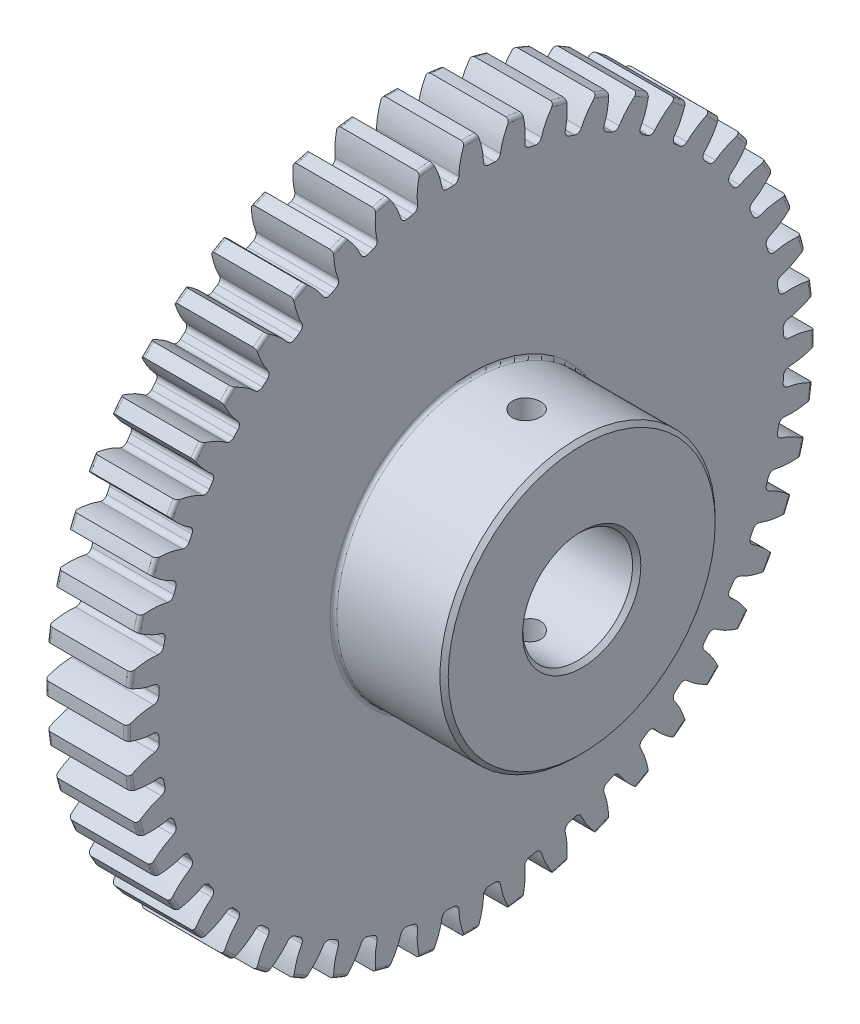
SolidWorks part; units mm, degrees
material "Delrin 2700 NC010, Low Viscosity Acetal Copolymer (SS)"
ref_plane "Front Plane" through (0, 0, 0) normal (0, 0, 1) x (1, 0, 0)
ref_plane "Top Plane" through (0, 0, 0) normal (0, 1, 0) x (1, 0, 0)
ref_plane "Right Plane" through (0, 0, 0) normal (1, 0, 0) x (0, 0, -1)
sketch "Sketch1" plane through (0, 0, 0) normal (0, 0, 1) x (1, 0, 0)
  line L0 (-2.3749, 19.8438) -> (-2.3749, 0)
  line L1 (-2.3749, 0) -> (2.3749, 0)
  line L2 (2.3749, 0) -> (2.3749, 19.8438)
  line L3 (2.3749, 19.8438) -> (-2.3749, 19.8438)
  line L4 (-2.3749, 0) -> (2.3749, 0) construction
revolve "Revolve1" add sketch "Sketch1" angle 360 about L4 reverse direction yes
sketch "Sketch2" plane through (-2.3749, 0, 0) normal (-1, 0, 0) x (0, 0, 1)
  arc A0 (0.7316, 18.0319) -> (1.6283, 17.9731) centre (0, 0) cw
  arc A1 (2.2123, 19.72) -> (0.3806, 19.8401) centre (0, 0) ccw
  spline S0 degree 3 poles (0.3806, 19.8401) (0.4054, 19.7738) (0.4294, 19.7071) (0.4523, 19.6401) (0.5249, 19.4282) (0.5865, 19.212) (0.6329, 18.9928) (0.6803, 18.7688) (0.6967, 18.5388) (0.7099, 18.3101) (0.7153, 18.2172) (0.7242, 18.1246) (0.7316, 18.0319) knots -0.000212 -0.000212 -0.000212 -0.000212 0 0 0 0.000672 0.000672 0.000672 0.001361 0.001361 0.001361 0.00164 0.00164 0.00164 0.00164
  spline S1 degree 3 poles (1.6283, 17.9731) (1.6477, 18.0641) (1.6686, 18.1548) (1.6861, 18.2461) (1.7281, 18.4663) (1.7727, 18.6874) (1.8467, 18.8989) (1.9223, 19.115) (2.0133, 19.326) (2.1151, 19.5311) (2.1466, 19.5946) (2.179, 19.6575) (2.2123, 19.72) knots -0.000279 -0.000279 -0.000279 -0.000279 0 0 0 0.000672 0.000672 0.000672 0.001357 0.001357 0.001357 0.001569 0.001569 0.001569 0.001569
extrude "Cut-Extrude1" cut sketch "Sketch2" against normal through all
sketch "Sketch3" plane through (-2.3749, 0, 0) normal (-1, 0, 0) x (0, 0, 1)
  arc A0 (3.079, 17.7821) -> (3.9603, 17.6068) centre (0, 0) cw
  arc A1 (4.7674, 19.2626) -> (2.967, 19.6207) centre (0, 0) ccw
  spline S0 degree 3 poles (2.967, 19.6207) (2.983, 19.5517) (2.998, 19.4825) (3.012, 19.413) (3.0562, 19.1935) (3.0891, 18.9711) (3.1065, 18.7477) (3.1243, 18.5194) (3.1106, 18.2892) (3.0938, 18.0608) (3.087, 17.968) (3.0838, 17.875) (3.079, 17.7821) knots -0.000212 -0.000212 -0.000212 -0.000212 0 0 0 0.000672 0.000672 0.000672 0.001361 0.001361 0.001361 0.00164 0.00164 0.00164 0.00164
  spline S1 degree 3 poles (3.9603, 17.6068) (3.9914, 17.6945) (4.024, 17.7816) (4.0533, 17.87) (4.1236, 18.0827) (4.1967, 18.2962) (4.2977, 18.4962) (4.4008, 18.7006) (4.5187, 18.8979) (4.6463, 19.088) (4.6858, 19.1467) (4.7262, 19.2049) (4.7674, 19.2626) knots -0.000279 -0.000279 -0.000279 -0.000279 0 0 0 0.000672 0.000672 0.000672 0.001357 0.001357 0.001357 0.001569 0.001569 0.001569 0.001569
extrude "Cut-Extrude2" cut sketch "Sketch3" against normal through all
sketch "Sketch4" plane through (-2.3749, 0, 0) normal (-1, 0, 0) x (0, 0, 1)
  arc A0 (5.3737, 17.2281) -> (6.2246, 16.9392) centre (0, 0) cw
  arc A1 (7.2408, 18.4755) -> (5.5026, 19.0656) centre (0, 0) ccw
  spline S0 degree 3 poles (5.5026, 19.0656) (5.5094, 18.9951) (5.5153, 18.9245) (5.5201, 18.8538) (5.5354, 18.6303) (5.5389, 18.4055) (5.527, 18.1819) (5.5148, 17.9532) (5.4712, 17.7267) (5.4248, 17.5025) (5.4059, 17.4114) (5.3906, 17.3196) (5.3737, 17.2281) knots -0.000212 -0.000212 -0.000212 -0.000212 0 0 0 0.000672 0.000672 0.000672 0.001361 0.001361 0.001361 0.00164 0.00164 0.00164 0.00164
  spline S1 degree 3 poles (6.2246, 16.9392) (6.2669, 17.0221) (6.3106, 17.1043) (6.3511, 17.188) (6.4486, 17.3898) (6.5489, 17.5918) (6.6752, 17.777) (6.8041, 17.9662) (6.9467, 18.1464) (7.0981, 18.3182) (7.1449, 18.3713) (7.1925, 18.4237) (7.2408, 18.4755) knots -0.000279 -0.000279 -0.000279 -0.000279 0 0 0 0.000672 0.000672 0.000672 0.001357 0.001357 0.001357 0.001569 0.001569 0.001569 0.001569
extrude "Cut-Extrude3" cut sketch "Sketch4" against normal through all
sketch "Sketch5" plane through (-2.3749, 0, 0) normal (-1, 0, 0) x (0, 0, 1)
  arc A0 (7.5764, 16.3793) -> (8.3824, 15.9819) centre (0, 0) cw
  arc A1 (9.5904, 17.3723) -> (7.9441, 18.1842) centre (0, 0) ccw
  spline S0 degree 3 poles (7.9441, 18.1842) (7.9417, 18.1134) (7.9383, 18.0427) (7.9338, 17.972) (7.9197, 17.7484) (7.894, 17.5251) (7.8529, 17.3049) (7.811, 17.0798) (7.7382, 16.8609) (7.6629, 16.6447) (7.6323, 16.5568) (7.6051, 16.4678) (7.5764, 16.3793) knots -0.000212 -0.000212 -0.000212 -0.000212 0 0 0 0.000672 0.000672 0.000672 0.001361 0.001361 0.001361 0.00164 0.00164 0.00164 0.00164
  spline S1 degree 3 poles (8.3824, 15.9819) (8.4351, 16.0585) (8.4892, 16.1342) (8.5402, 16.212) (8.6633, 16.3993) (8.7891, 16.5865) (8.9384, 16.7536) (9.091, 16.9244) (9.2558, 17.0845) (9.4283, 17.235) (9.4817, 17.2816) (9.5358, 17.3273) (9.5904, 17.3723) knots -0.000279 -0.000279 -0.000279 -0.000279 0 0 0 0.000672 0.000672 0.000672 0.001357 0.001357 0.001357 0.001569 0.001569 0.001569 0.001569
extrude "Cut-Extrude4" cut sketch "Sketch5" against normal through all
sketch "Sketch6" plane through (-2.3749, 0, 0) normal (-1, 0, 0) x (0, 0, 1)
  arc A0 (9.6495, 15.2503) -> (10.3967, 14.751) centre (0, 0) cw
  arc A1 (11.7759, 15.9719) -> (10.2497, 16.9917) centre (0, 0) ccw
  spline S0 degree 3 poles (10.2497, 16.9917) (10.238, 16.9219) (10.2254, 16.8522) (10.2118, 16.7827) (10.1686, 16.5629) (10.1139, 16.3448) (10.0445, 16.1318) (9.9735, 15.9141) (9.8728, 15.7067) (9.7699, 15.5021) (9.7281, 15.4189) (9.6895, 15.3342) (9.6495, 15.2503) knots -0.000212 -0.000212 -0.000212 -0.000212 0 0 0 0.000672 0.000672 0.000672 0.001361 0.001361 0.001361 0.00164 0.00164 0.00164 0.00164
  spline S1 degree 3 poles (10.3967, 14.751) (10.459, 14.8201) (10.5225, 14.8882) (10.5833, 14.9586) (10.7297, 15.1282) (10.8789, 15.2974) (11.0487, 15.4436) (11.2223, 15.593) (11.4066, 15.7302) (11.5973, 15.8569) (11.6563, 15.8961) (11.7159, 15.9344) (11.7759, 15.9719) knots -0.000279 -0.000279 -0.000279 -0.000279 0 0 0 0.000672 0.000672 0.000672 0.001357 0.001357 0.001357 0.001569 0.001569 0.001569 0.001569
extrude "Cut-Extrude5" cut sketch "Sketch6" against normal through all
sketch "Sketch7" plane through (-2.3749, 0, 0) normal (-1, 0, 0) x (0, 0, 1)
  arc A0 (11.5575, 13.8603) -> (12.2331, 13.2678) centre (0, 0) cw
  arc A1 (13.7599, 14.2982) -> (12.3798, 15.5085) centre (0, 0) ccw
  spline S0 degree 3 poles (12.3798, 15.5085) (12.3592, 15.4408) (12.3376, 15.3733) (12.315, 15.3062) (12.2435, 15.0939) (12.1608, 14.8848) (12.0642, 14.6828) (11.9654, 14.4761) (11.8384, 14.2836) (11.7097, 14.0942) (11.6574, 14.0173) (11.6081, 13.9383) (11.5575, 13.8603) knots -0.000212 -0.000212 -0.000212 -0.000212 0 0 0 0.000672 0.000672 0.000672 0.001361 0.001361 0.001361 0.00164 0.00164 0.00164 0.00164
  spline S1 degree 3 poles (12.2331, 13.2678) (12.3039, 13.3282) (12.3757, 13.3873) (12.4452, 13.4492) (12.6125, 13.5983) (12.7825, 13.7466) (12.97, 13.8693) (13.1615, 13.9948) (13.3622, 14.1067) (13.5678, 14.2075) (13.6314, 14.2387) (13.6955, 14.2689) (13.7599, 14.2982) knots -0.000279 -0.000279 -0.000279 -0.000279 0 0 0 0.000672 0.000672 0.000672 0.001357 0.001357 0.001357 0.001569 0.001569 0.001569 0.001569
extrude "Cut-Extrude6" cut sketch "Sketch7" against normal through all
sketch "Sketch8" plane through (-2.3749, 0, 0) normal (-1, 0, 0) x (0, 0, 1)
  arc A0 (13.2678, 12.2331) -> (13.8603, 11.5575) centre (0, 0) cw
  arc A1 (15.5085, 12.3798) -> (14.2982, 13.7599) centre (0, 0) ccw
  spline S0 degree 3 poles (14.2982, 13.7599) (14.2689, 13.6955) (14.2387, 13.6314) (14.2075, 13.5678) (14.1089, 13.3667) (13.9996, 13.1702) (13.8775, 12.9824) (13.7526, 12.7905) (13.6016, 12.6162) (13.4492, 12.4452) (13.3873, 12.3757) (13.3282, 12.3039) (13.2678, 12.2331) knots -0.000212 -0.000212 -0.000212 -0.000212 0 0 0 0.000672 0.000672 0.000672 0.001361 0.001361 0.001361 0.00164 0.00164 0.00164 0.00164
  spline S1 degree 3 poles (13.8603, 11.5575) (13.9383, 11.6081) (14.0173, 11.6574) (14.0942, 11.7097) (14.2796, 11.8357) (14.4675, 11.9605) (14.6694, 12.0578) (14.8756, 12.1571) (15.0892, 12.2419) (15.3062, 12.315) (15.3733, 12.3376) (15.4408, 12.3592) (15.5085, 12.3798) knots -0.000279 -0.000279 -0.000279 -0.000279 0 0 0 0.000672 0.000672 0.000672 0.001357 0.001357 0.001357 0.001569 0.001569 0.001569 0.001569
extrude "Cut-Extrude7" cut sketch "Sketch8" against normal through all
sketch "Sketch9" plane through (-2.3749, 0, 0) normal (-1, 0, 0) x (0, 0, 1)
  arc A0 (14.751, 10.3967) -> (15.2503, 9.6495) centre (0, 0) cw
  arc A1 (16.9917, 10.2497) -> (15.9719, 11.7759) centre (0, 0) ccw
  spline S0 degree 3 poles (15.9719, 11.7759) (15.9344, 11.7159) (15.8961, 11.6563) (15.8569, 11.5973) (15.7329, 11.4107) (15.5989, 11.2302) (15.4533, 11.06) (15.3044, 10.886) (15.1319, 10.7329) (14.9586, 10.5833) (14.8882, 10.5225) (14.8201, 10.459) (14.751, 10.3967) knots -0.000212 -0.000212 -0.000212 -0.000212 0 0 0 0.000672 0.000672 0.000672 0.001361 0.001361 0.001361 0.00164 0.00164 0.00164 0.00164
  spline S1 degree 3 poles (15.2503, 9.6495) (15.3342, 9.6895) (15.4189, 9.7281) (15.5021, 9.7699) (15.7023, 9.8706) (15.9049, 9.9698) (16.1177, 10.0399) (16.3352, 10.1114) (16.558, 10.1677) (16.7827, 10.2118) (16.8522, 10.2254) (16.9219, 10.238) (16.9917, 10.2497) knots -0.000279 -0.000279 -0.000279 -0.000279 0 0 0 0.000672 0.000672 0.000672 0.001357 0.001357 0.001357 0.001569 0.001569 0.001569 0.001569
extrude "Cut-Extrude8" cut sketch "Sketch9" against normal through all
sketch "Sketch10" plane through (-2.3749, 0, 0) normal (-1, 0, 0) x (0, 0, 1)
  arc A0 (15.9819, 8.3824) -> (16.3793, 7.5764) centre (0, 0) cw
  arc A1 (18.1842, 7.9441) -> (17.3723, 9.5904) centre (0, 0) ccw
  spline S0 degree 3 poles (17.3723, 9.5904) (17.3273, 9.5358) (17.2816, 9.4817) (17.235, 9.4283) (17.0877, 9.2596) (16.9313, 9.0981) (16.7647, 8.9483) (16.5944, 8.7953) (16.4034, 8.666) (16.212, 8.5402) (16.1342, 8.4892) (16.0585, 8.4351) (15.9819, 8.3824) knots -0.000212 -0.000212 -0.000212 -0.000212 0 0 0 0.000672 0.000672 0.000672 0.001361 0.001361 0.001361 0.00164 0.00164 0.00164 0.00164
  spline S1 degree 3 poles (16.3793, 7.5764) (16.4678, 7.6051) (16.5568, 7.6323) (16.6447, 7.6629) (16.8563, 7.7366) (17.0701, 7.8085) (17.2903, 7.8502) (17.5152, 7.8928) (17.7435, 7.9194) (17.972, 7.9338) (18.0427, 7.9383) (18.1134, 7.9417) (18.1842, 7.9441) knots -0.000279 -0.000279 -0.000279 -0.000279 0 0 0 0.000672 0.000672 0.000672 0.001357 0.001357 0.001357 0.001569 0.001569 0.001569 0.001569
extrude "Cut-Extrude9" cut sketch "Sketch10" against normal through all
sketch "Sketch11" plane through (-2.3749, 0, 0) normal (-1, 0, 0) x (0, 0, 1)
  arc A0 (16.9392, 6.2246) -> (17.2281, 5.3737) centre (0, 0) cw
  arc A1 (19.0656, 5.5026) -> (18.4755, 7.2408) centre (0, 0) ccw
  spline S0 degree 3 poles (18.4755, 7.2408) (18.4237, 7.1925) (18.3713, 7.1449) (18.3182, 7.0981) (18.1501, 6.9499) (17.974, 6.8102) (17.7893, 6.6835) (17.6004, 6.554) (17.3942, 6.4508) (17.188, 6.3511) (17.1043, 6.3106) (17.0221, 6.2669) (16.9392, 6.2246) knots -0.000212 -0.000212 -0.000212 -0.000212 0 0 0 0.000672 0.000672 0.000672 0.001361 0.001361 0.001361 0.00164 0.00164 0.00164 0.00164
  spline S1 degree 3 poles (17.2281, 5.3737) (17.3196, 5.3906) (17.4114, 5.4059) (17.5025, 5.4248) (17.7219, 5.4702) (17.9433, 5.5136) (18.167, 5.5262) (18.3956, 5.539) (18.6254, 5.5357) (18.8538, 5.5201) (18.9245, 5.5153) (18.9951, 5.5094) (19.0656, 5.5026) knots -0.000279 -0.000279 -0.000279 -0.000279 0 0 0 0.000672 0.000672 0.000672 0.001357 0.001357 0.001357 0.001569 0.001569 0.001569 0.001569
extrude "Cut-Extrude10" cut sketch "Sketch11" against normal through all
sketch "Sketch12" plane through (-2.3749, 0, 0) normal (-1, 0, 0) x (0, 0, 1)
  arc A0 (17.6068, 3.9603) -> (17.7821, 3.079) centre (0, 0) cw
  arc A1 (19.6207, 2.967) -> (19.2626, 4.7674) centre (0, 0) ccw
  spline S0 degree 3 poles (19.2626, 4.7674) (19.2049, 4.7262) (19.1467, 4.6858) (19.088, 4.6463) (18.902, 4.5214) (18.7091, 4.4059) (18.5095, 4.3044) (18.3053, 4.2006) (18.0874, 4.1252) (17.87, 4.0533) (17.7816, 4.024) (17.6945, 3.9914) (17.6068, 3.9603) knots -0.000212 -0.000212 -0.000212 -0.000212 0 0 0 0.000672 0.000672 0.000672 0.001361 0.001361 0.001361 0.00164 0.00164 0.00164 0.00164
  spline S1 degree 3 poles (17.7821, 3.079) (17.875, 3.0838) (17.968, 3.087) (18.0608, 3.0938) (18.2843, 3.1102) (18.5095, 3.1244) (18.7329, 3.1076) (18.9612, 3.0906) (19.1886, 3.0572) (19.413, 3.012) (19.4825, 2.998) (19.5517, 2.983) (19.6207, 2.967) knots -0.000279 -0.000279 -0.000279 -0.000279 0 0 0 0.000672 0.000672 0.000672 0.001357 0.001357 0.001357 0.001569 0.001569 0.001569 0.001569
extrude "Cut-Extrude11" cut sketch "Sketch12" against normal through all
sketch "Sketch13" plane through (-2.3749, 0, 0) normal (-1, 0, 0) x (0, 0, 1)
  arc A0 (17.9731, 1.6283) -> (18.0319, 0.7316) centre (0, 0) cw
  arc A1 (19.8401, 0.3806) -> (19.72, 2.2123) centre (0, 0) ccw
  spline S0 degree 3 poles (19.72, 2.2123) (19.6575, 2.179) (19.5946, 2.1466) (19.5311, 2.1151) (19.3305, 2.0155) (19.1242, 1.9262) (18.9129, 1.8516) (18.697, 1.7754) (18.4711, 1.729) (18.2461, 1.6861) (18.1548, 1.6686) (18.0641, 1.6477) (17.9731, 1.6283) knots -0.000212 -0.000212 -0.000212 -0.000212 0 0 0 0.000672 0.000672 0.000672 0.001361 0.001361 0.001361 0.00164 0.00164 0.00164 0.00164
  spline S1 degree 3 poles (18.0319, 0.7316) (18.1246, 0.7243) (18.2172, 0.7153) (18.3101, 0.7099) (18.5338, 0.697) (18.7589, 0.6817) (18.9783, 0.6359) (19.2024, 0.5892) (19.4235, 0.5265) (19.6401, 0.4523) (19.7071, 0.4294) (19.7738, 0.4054) (19.8401, 0.3806) knots -0.000279 -0.000279 -0.000279 -0.000279 0 0 0 0.000672 0.000672 0.000672 0.001357 0.001357 0.001357 0.001569 0.001569 0.001569 0.001569
extrude "Cut-Extrude12" cut sketch "Sketch13" against normal through all
sketch "Sketch14" plane through (-2.3749, 0, 0) normal (-1, 0, 0) x (0, 0, 1)
  arc A0 (18.0319, -0.7316) -> (17.9731, -1.6283) centre (0, 0) cw
  arc A1 (19.72, -2.2123) -> (19.8401, -0.3806) centre (0, 0) ccw
  spline S0 degree 3 poles (19.8401, -0.3806) (19.7738, -0.4054) (19.7071, -0.4294) (19.6401, -0.4523) (19.4282, -0.5249) (19.212, -0.5865) (18.9928, -0.6329) (18.7688, -0.6803) (18.5388, -0.6967) (18.3101, -0.7099) (18.2172, -0.7153) (18.1246, -0.7242) (18.0319, -0.7316) knots -0.000212 -0.000212 -0.000212 -0.000212 0 0 0 0.000672 0.000672 0.000672 0.001361 0.001361 0.001361 0.00164 0.00164 0.00164 0.00164
  spline S1 degree 3 poles (17.9731, -1.6283) (18.0641, -1.6477) (18.1548, -1.6686) (18.2461, -1.6861) (18.4663, -1.7281) (18.6874, -1.7727) (18.8989, -1.8467) (19.115, -1.9223) (19.326, -2.0133) (19.5311, -2.1151) (19.5946, -2.1466) (19.6575, -2.179) (19.72, -2.2123) knots -0.000279 -0.000279 -0.000279 -0.000279 0 0 0 0.000672 0.000672 0.000672 0.001357 0.001357 0.001357 0.001569 0.001569 0.001569 0.001569
extrude "Cut-Extrude13" cut sketch "Sketch14" against normal through all
sketch "Sketch15" plane through (-2.3749, 0, 0) normal (-1, 0, 0) x (0, 0, 1)
  arc A0 (17.7821, -3.079) -> (17.6068, -3.9603) centre (0, 0) cw
  arc A1 (19.2626, -4.7674) -> (19.6207, -2.967) centre (0, 0) ccw
  spline S0 degree 3 poles (19.6207, -2.967) (19.5517, -2.983) (19.4825, -2.998) (19.413, -3.012) (19.1935, -3.0562) (18.9711, -3.0891) (18.7477, -3.1065) (18.5194, -3.1243) (18.2892, -3.1106) (18.0608, -3.0938) (17.968, -3.087) (17.875, -3.0838) (17.7821, -3.079) knots -0.000212 -0.000212 -0.000212 -0.000212 0 0 0 0.000672 0.000672 0.000672 0.001361 0.001361 0.001361 0.00164 0.00164 0.00164 0.00164
  spline S1 degree 3 poles (17.6068, -3.9603) (17.6945, -3.9914) (17.7816, -4.024) (17.87, -4.0533) (18.0827, -4.1236) (18.2962, -4.1967) (18.4962, -4.2977) (18.7006, -4.4008) (18.8979, -4.5187) (19.088, -4.6463) (19.1467, -4.6858) (19.2049, -4.7262) (19.2626, -4.7674) knots -0.000279 -0.000279 -0.000279 -0.000279 0 0 0 0.000672 0.000672 0.000672 0.001357 0.001357 0.001357 0.001569 0.001569 0.001569 0.001569
extrude "Cut-Extrude14" cut sketch "Sketch15" against normal through all
sketch "Sketch16" plane through (-2.3749, 0, 0) normal (-1, 0, 0) x (0, 0, 1)
  arc A0 (17.2281, -5.3737) -> (16.9392, -6.2246) centre (0, 0) cw
  arc A1 (18.4755, -7.2408) -> (19.0656, -5.5026) centre (0, 0) ccw
  spline S0 degree 3 poles (19.0656, -5.5026) (18.9951, -5.5094) (18.9245, -5.5153) (18.8538, -5.5201) (18.6303, -5.5354) (18.4055, -5.5389) (18.1819, -5.527) (17.9532, -5.5148) (17.7267, -5.4712) (17.5025, -5.4248) (17.4114, -5.4059) (17.3196, -5.3906) (17.2281, -5.3737) knots -0.000212 -0.000212 -0.000212 -0.000212 0 0 0 0.000672 0.000672 0.000672 0.001361 0.001361 0.001361 0.00164 0.00164 0.00164 0.00164
  spline S1 degree 3 poles (16.9392, -6.2246) (17.0221, -6.2669) (17.1043, -6.3106) (17.188, -6.3511) (17.3898, -6.4486) (17.5918, -6.5489) (17.777, -6.6752) (17.9662, -6.8041) (18.1464, -6.9467) (18.3182, -7.0981) (18.3713, -7.1449) (18.4237, -7.1925) (18.4755, -7.2408) knots -0.000279 -0.000279 -0.000279 -0.000279 0 0 0 0.000672 0.000672 0.000672 0.001357 0.001357 0.001357 0.001569 0.001569 0.001569 0.001569
extrude "Cut-Extrude15" cut sketch "Sketch16" against normal through all
sketch "Sketch17" plane through (-2.3749, 0, 0) normal (-1, 0, 0) x (0, 0, 1)
  arc A0 (16.3793, -7.5764) -> (15.9819, -8.3824) centre (0, 0) cw
  arc A1 (17.3723, -9.5904) -> (18.1842, -7.9441) centre (0, 0) ccw
  spline S0 degree 3 poles (18.1842, -7.9441) (18.1134, -7.9417) (18.0427, -7.9383) (17.972, -7.9338) (17.7484, -7.9197) (17.5251, -7.894) (17.3049, -7.8529) (17.0798, -7.811) (16.8609, -7.7382) (16.6447, -7.6629) (16.5568, -7.6323) (16.4678, -7.6051) (16.3793, -7.5764) knots -0.000212 -0.000212 -0.000212 -0.000212 0 0 0 0.000672 0.000672 0.000672 0.001361 0.001361 0.001361 0.00164 0.00164 0.00164 0.00164
  spline S1 degree 3 poles (15.9819, -8.3824) (16.0585, -8.4351) (16.1342, -8.4892) (16.212, -8.5402) (16.3993, -8.6633) (16.5865, -8.7891) (16.7536, -8.9384) (16.9244, -9.091) (17.0845, -9.2558) (17.235, -9.4283) (17.2816, -9.4817) (17.3273, -9.5358) (17.3723, -9.5904) knots -0.000279 -0.000279 -0.000279 -0.000279 0 0 0 0.000672 0.000672 0.000672 0.001357 0.001357 0.001357 0.001569 0.001569 0.001569 0.001569
extrude "Cut-Extrude16" cut sketch "Sketch17" against normal through all
sketch "Sketch18" plane through (-2.3749, 0, 0) normal (-1, 0, 0) x (0, 0, 1)
  arc A0 (15.2503, -9.6495) -> (14.751, -10.3967) centre (0, 0) cw
  arc A1 (15.9719, -11.7759) -> (16.9917, -10.2497) centre (0, 0) ccw
  spline S0 degree 3 poles (16.9917, -10.2497) (16.9219, -10.238) (16.8522, -10.2254) (16.7827, -10.2118) (16.5629, -10.1686) (16.3448, -10.1139) (16.1318, -10.0445) (15.9141, -9.9735) (15.7067, -9.8728) (15.5021, -9.7699) (15.4189, -9.7281) (15.3342, -9.6895) (15.2503, -9.6495) knots -0.000212 -0.000212 -0.000212 -0.000212 0 0 0 0.000672 0.000672 0.000672 0.001361 0.001361 0.001361 0.00164 0.00164 0.00164 0.00164
  spline S1 degree 3 poles (14.751, -10.3967) (14.8201, -10.459) (14.8882, -10.5225) (14.9586, -10.5833) (15.1282, -10.7297) (15.2974, -10.8789) (15.4436, -11.0487) (15.593, -11.2223) (15.7302, -11.4066) (15.8569, -11.5973) (15.8961, -11.6563) (15.9344, -11.7159) (15.9719, -11.7759) knots -0.000279 -0.000279 -0.000279 -0.000279 0 0 0 0.000672 0.000672 0.000672 0.001357 0.001357 0.001357 0.001569 0.001569 0.001569 0.001569
extrude "Cut-Extrude17" cut sketch "Sketch18" against normal through all
sketch "Sketch19" plane through (-2.3749, 0, 0) normal (-1, 0, 0) x (0, 0, 1)
  arc A0 (13.8603, -11.5575) -> (13.2678, -12.2331) centre (0, 0) cw
  arc A1 (14.2982, -13.7599) -> (15.5085, -12.3798) centre (0, 0) ccw
  spline S0 degree 3 poles (15.5085, -12.3798) (15.4408, -12.3592) (15.3733, -12.3376) (15.3062, -12.315) (15.0939, -12.2435) (14.8848, -12.1608) (14.6828, -12.0642) (14.4761, -11.9654) (14.2836, -11.8384) (14.0942, -11.7097) (14.0173, -11.6574) (13.9383, -11.6081) (13.8603, -11.5575) knots -0.000212 -0.000212 -0.000212 -0.000212 0 0 0 0.000672 0.000672 0.000672 0.001361 0.001361 0.001361 0.00164 0.00164 0.00164 0.00164
  spline S1 degree 3 poles (13.2678, -12.2331) (13.3282, -12.3039) (13.3873, -12.3757) (13.4492, -12.4452) (13.5983, -12.6125) (13.7466, -12.7825) (13.8693, -12.97) (13.9948, -13.1615) (14.1067, -13.3622) (14.2075, -13.5678) (14.2387, -13.6314) (14.2689, -13.6955) (14.2982, -13.7599) knots -0.000279 -0.000279 -0.000279 -0.000279 0 0 0 0.000672 0.000672 0.000672 0.001357 0.001357 0.001357 0.001569 0.001569 0.001569 0.001569
extrude "Cut-Extrude18" cut sketch "Sketch19" against normal through all
sketch "Sketch20" plane through (-2.3749, 0, 0) normal (-1, 0, 0) x (0, 0, 1)
  arc A0 (12.2331, -13.2678) -> (11.5575, -13.8603) centre (0, 0) cw
  arc A1 (12.3798, -15.5085) -> (13.7599, -14.2982) centre (0, 0) ccw
  spline S0 degree 3 poles (13.7599, -14.2982) (13.6955, -14.2689) (13.6314, -14.2387) (13.5678, -14.2075) (13.3667, -14.1089) (13.1702, -13.9996) (12.9824, -13.8775) (12.7905, -13.7526) (12.6162, -13.6016) (12.4452, -13.4492) (12.3757, -13.3873) (12.3039, -13.3282) (12.2331, -13.2678) knots -0.000212 -0.000212 -0.000212 -0.000212 0 0 0 0.000672 0.000672 0.000672 0.001361 0.001361 0.001361 0.00164 0.00164 0.00164 0.00164
  spline S1 degree 3 poles (11.5575, -13.8603) (11.6081, -13.9383) (11.6574, -14.0173) (11.7097, -14.0942) (11.8357, -14.2796) (11.9605, -14.4675) (12.0578, -14.6694) (12.1571, -14.8756) (12.2419, -15.0892) (12.315, -15.3062) (12.3376, -15.3733) (12.3592, -15.4408) (12.3798, -15.5085) knots -0.000279 -0.000279 -0.000279 -0.000279 0 0 0 0.000672 0.000672 0.000672 0.001357 0.001357 0.001357 0.001569 0.001569 0.001569 0.001569
extrude "Cut-Extrude19" cut sketch "Sketch20" against normal through all
sketch "Sketch21" plane through (-2.3749, 0, 0) normal (-1, 0, 0) x (0, 0, 1)
  arc A0 (10.3967, -14.751) -> (9.6495, -15.2503) centre (0, 0) cw
  arc A1 (10.2497, -16.9917) -> (11.7759, -15.9719) centre (0, 0) ccw
  spline S0 degree 3 poles (11.7759, -15.9719) (11.7159, -15.9344) (11.6563, -15.8961) (11.5973, -15.8569) (11.4107, -15.7329) (11.2302, -15.5989) (11.06, -15.4533) (10.886, -15.3044) (10.7329, -15.1319) (10.5833, -14.9586) (10.5225, -14.8882) (10.459, -14.8201) (10.3967, -14.751) knots -0.000212 -0.000212 -0.000212 -0.000212 0 0 0 0.000672 0.000672 0.000672 0.001361 0.001361 0.001361 0.00164 0.00164 0.00164 0.00164
  spline S1 degree 3 poles (9.6495, -15.2503) (9.6895, -15.3342) (9.7281, -15.4189) (9.7699, -15.5021) (9.8706, -15.7023) (9.9698, -15.9049) (10.0399, -16.1177) (10.1114, -16.3352) (10.1677, -16.558) (10.2118, -16.7827) (10.2254, -16.8522) (10.238, -16.9219) (10.2497, -16.9917) knots -0.000279 -0.000279 -0.000279 -0.000279 0 0 0 0.000672 0.000672 0.000672 0.001357 0.001357 0.001357 0.001569 0.001569 0.001569 0.001569
extrude "Cut-Extrude20" cut sketch "Sketch21" against normal through all
sketch "Sketch22" plane through (-2.3749, 0, 0) normal (-1, 0, 0) x (0, 0, 1)
  arc A0 (8.3824, -15.9819) -> (7.5764, -16.3793) centre (0, 0) cw
  arc A1 (7.9441, -18.1842) -> (9.5904, -17.3723) centre (0, 0) ccw
  spline S0 degree 3 poles (9.5904, -17.3723) (9.5358, -17.3273) (9.4817, -17.2816) (9.4283, -17.235) (9.2596, -17.0877) (9.0981, -16.9313) (8.9483, -16.7647) (8.7953, -16.5944) (8.666, -16.4034) (8.5402, -16.212) (8.4892, -16.1342) (8.4351, -16.0585) (8.3824, -15.9819) knots -0.000212 -0.000212 -0.000212 -0.000212 0 0 0 0.000672 0.000672 0.000672 0.001361 0.001361 0.001361 0.00164 0.00164 0.00164 0.00164
  spline S1 degree 3 poles (7.5764, -16.3793) (7.6051, -16.4678) (7.6323, -16.5568) (7.6629, -16.6447) (7.7366, -16.8563) (7.8085, -17.0701) (7.8502, -17.2903) (7.8928, -17.5152) (7.9194, -17.7435) (7.9338, -17.972) (7.9383, -18.0427) (7.9417, -18.1134) (7.9441, -18.1842) knots -0.000279 -0.000279 -0.000279 -0.000279 0 0 0 0.000672 0.000672 0.000672 0.001357 0.001357 0.001357 0.001569 0.001569 0.001569 0.001569
extrude "Cut-Extrude21" cut sketch "Sketch22" against normal through all
sketch "Sketch23" plane through (-2.3749, 0, 0) normal (-1, 0, 0) x (0, 0, 1)
  arc A0 (6.2246, -16.9392) -> (5.3737, -17.2281) centre (0, 0) cw
  arc A1 (5.5026, -19.0656) -> (7.2408, -18.4755) centre (0, 0) ccw
  spline S0 degree 3 poles (7.2408, -18.4755) (7.1925, -18.4237) (7.1449, -18.3713) (7.0981, -18.3182) (6.9499, -18.1501) (6.8102, -17.974) (6.6835, -17.7893) (6.554, -17.6004) (6.4508, -17.3942) (6.3511, -17.188) (6.3106, -17.1043) (6.2669, -17.0221) (6.2246, -16.9392) knots -0.000212 -0.000212 -0.000212 -0.000212 0 0 0 0.000672 0.000672 0.000672 0.001361 0.001361 0.001361 0.00164 0.00164 0.00164 0.00164
  spline S1 degree 3 poles (5.3737, -17.2281) (5.3906, -17.3196) (5.4059, -17.4114) (5.4248, -17.5025) (5.4702, -17.7219) (5.5136, -17.9433) (5.5262, -18.167) (5.539, -18.3956) (5.5357, -18.6254) (5.5201, -18.8538) (5.5153, -18.9245) (5.5094, -18.9951) (5.5026, -19.0656) knots -0.000279 -0.000279 -0.000279 -0.000279 0 0 0 0.000672 0.000672 0.000672 0.001357 0.001357 0.001357 0.001569 0.001569 0.001569 0.001569
extrude "Cut-Extrude22" cut sketch "Sketch23" against normal through all
sketch "Sketch24" plane through (-2.3749, 0, 0) normal (-1, 0, 0) x (0, 0, 1)
  arc A0 (3.9603, -17.6068) -> (3.079, -17.7821) centre (0, 0) cw
  arc A1 (2.967, -19.6207) -> (4.7674, -19.2626) centre (0, 0) ccw
  spline S0 degree 3 poles (4.7674, -19.2626) (4.7262, -19.2049) (4.6858, -19.1467) (4.6463, -19.088) (4.5214, -18.902) (4.4059, -18.7091) (4.3044, -18.5095) (4.2006, -18.3053) (4.1252, -18.0874) (4.0533, -17.87) (4.024, -17.7816) (3.9914, -17.6945) (3.9603, -17.6068) knots -0.000212 -0.000212 -0.000212 -0.000212 0 0 0 0.000672 0.000672 0.000672 0.001361 0.001361 0.001361 0.00164 0.00164 0.00164 0.00164
  spline S1 degree 3 poles (3.079, -17.7821) (3.0838, -17.875) (3.087, -17.968) (3.0938, -18.0608) (3.1102, -18.2843) (3.1244, -18.5095) (3.1076, -18.7329) (3.0906, -18.9612) (3.0572, -19.1886) (3.012, -19.413) (2.998, -19.4825) (2.983, -19.5517) (2.967, -19.6207) knots -0.000279 -0.000279 -0.000279 -0.000279 0 0 0 0.000672 0.000672 0.000672 0.001357 0.001357 0.001357 0.001569 0.001569 0.001569 0.001569
extrude "Cut-Extrude23" cut sketch "Sketch24" against normal through all
sketch "Sketch25" plane through (-2.3749, 0, 0) normal (-1, 0, 0) x (0, 0, 1)
  arc A0 (1.6283, -17.9731) -> (0.7316, -18.0319) centre (0, 0) cw
  arc A1 (0.3806, -19.8401) -> (2.2123, -19.72) centre (0, 0) ccw
  spline S0 degree 3 poles (2.2123, -19.72) (2.179, -19.6575) (2.1466, -19.5946) (2.1151, -19.5311) (2.0155, -19.3305) (1.9262, -19.1242) (1.8516, -18.9129) (1.7754, -18.697) (1.729, -18.4711) (1.6861, -18.2461) (1.6686, -18.1548) (1.6477, -18.0641) (1.6283, -17.9731) knots -0.000212 -0.000212 -0.000212 -0.000212 0 0 0 0.000672 0.000672 0.000672 0.001361 0.001361 0.001361 0.00164 0.00164 0.00164 0.00164
  spline S1 degree 3 poles (0.7316, -18.0319) (0.7243, -18.1246) (0.7153, -18.2172) (0.7099, -18.3101) (0.697, -18.5338) (0.6817, -18.7589) (0.6359, -18.9783) (0.5892, -19.2024) (0.5265, -19.4235) (0.4523, -19.6401) (0.4294, -19.7071) (0.4054, -19.7738) (0.3806, -19.8401) knots -0.000279 -0.000279 -0.000279 -0.000279 0 0 0 0.000672 0.000672 0.000672 0.001357 0.001357 0.001357 0.001569 0.001569 0.001569 0.001569
extrude "Cut-Extrude24" cut sketch "Sketch25" against normal through all
sketch "Sketch26" plane through (-2.3749, 0, 0) normal (-1, 0, 0) x (0, 0, 1)
  arc A0 (-2.2123, -19.72) -> (-0.3806, -19.8401) centre (0, 0) ccw
  arc A1 (-0.7316, -18.0319) -> (-1.6283, -17.9731) centre (0, 0) cw
  spline S0 degree 3 poles (-0.3806, -19.8401) (-0.4054, -19.7738) (-0.4294, -19.7071) (-0.4523, -19.6401) (-0.5249, -19.4282) (-0.5865, -19.212) (-0.6329, -18.9928) (-0.6803, -18.7688) (-0.6967, -18.5388) (-0.7099, -18.3101) (-0.7153, -18.2172) (-0.7242, -18.1246) (-0.7316, -18.0319) knots -0.000212 -0.000212 -0.000212 -0.000212 0 0 0 0.000672 0.000672 0.000672 0.001361 0.001361 0.001361 0.00164 0.00164 0.00164 0.00164
  spline S1 degree 3 poles (-1.6283, -17.9731) (-1.6477, -18.0641) (-1.6686, -18.1548) (-1.6861, -18.2461) (-1.7281, -18.4663) (-1.7727, -18.6874) (-1.8467, -18.8989) (-1.9223, -19.115) (-2.0133, -19.326) (-2.1151, -19.5311) (-2.1466, -19.5946) (-2.179, -19.6575) (-2.2123, -19.72) knots -0.000279 -0.000279 -0.000279 -0.000279 0 0 0 0.000672 0.000672 0.000672 0.001357 0.001357 0.001357 0.001569 0.001569 0.001569 0.001569
extrude "Cut-Extrude25" cut sketch "Sketch26" against normal through all
sketch "Sketch27" plane through (-2.3749, 0, 0) normal (-1, 0, 0) x (0, 0, 1)
  arc A0 (-4.7674, -19.2626) -> (-2.967, -19.6207) centre (0, 0) ccw
  arc A1 (-3.079, -17.7821) -> (-3.9603, -17.6068) centre (0, 0) cw
  spline S0 degree 3 poles (-2.967, -19.6207) (-2.983, -19.5517) (-2.998, -19.4825) (-3.012, -19.413) (-3.0562, -19.1935) (-3.0891, -18.9711) (-3.1065, -18.7477) (-3.1243, -18.5194) (-3.1106, -18.2892) (-3.0938, -18.0608) (-3.087, -17.968) (-3.0838, -17.875) (-3.079, -17.7821) knots -0.000212 -0.000212 -0.000212 -0.000212 0 0 0 0.000672 0.000672 0.000672 0.001361 0.001361 0.001361 0.00164 0.00164 0.00164 0.00164
  spline S1 degree 3 poles (-3.9603, -17.6068) (-3.9914, -17.6945) (-4.024, -17.7816) (-4.0533, -17.87) (-4.1236, -18.0827) (-4.1967, -18.2962) (-4.2977, -18.4962) (-4.4008, -18.7006) (-4.5187, -18.8979) (-4.6463, -19.088) (-4.6858, -19.1467) (-4.7262, -19.2049) (-4.7674, -19.2626) knots -0.000279 -0.000279 -0.000279 -0.000279 0 0 0 0.000672 0.000672 0.000672 0.001357 0.001357 0.001357 0.001569 0.001569 0.001569 0.001569
extrude "Cut-Extrude26" cut sketch "Sketch27" against normal through all
sketch "Sketch28" plane through (-2.3749, 0, 0) normal (-1, 0, 0) x (0, 0, 1)
  arc A0 (-7.2408, -18.4755) -> (-5.5026, -19.0656) centre (0, 0) ccw
  arc A1 (-5.3737, -17.2281) -> (-6.2246, -16.9392) centre (0, 0) cw
  spline S0 degree 3 poles (-5.5026, -19.0656) (-5.5094, -18.9951) (-5.5153, -18.9245) (-5.5201, -18.8538) (-5.5354, -18.6303) (-5.5389, -18.4055) (-5.527, -18.1819) (-5.5148, -17.9532) (-5.4712, -17.7267) (-5.4248, -17.5025) (-5.4059, -17.4114) (-5.3906, -17.3196) (-5.3737, -17.2281) knots -0.000212 -0.000212 -0.000212 -0.000212 0 0 0 0.000672 0.000672 0.000672 0.001361 0.001361 0.001361 0.00164 0.00164 0.00164 0.00164
  spline S1 degree 3 poles (-6.2246, -16.9392) (-6.2669, -17.0221) (-6.3106, -17.1043) (-6.3511, -17.188) (-6.4486, -17.3898) (-6.5489, -17.5918) (-6.6752, -17.777) (-6.8041, -17.9662) (-6.9467, -18.1464) (-7.0981, -18.3182) (-7.1449, -18.3713) (-7.1925, -18.4237) (-7.2408, -18.4755) knots -0.000279 -0.000279 -0.000279 -0.000279 0 0 0 0.000672 0.000672 0.000672 0.001357 0.001357 0.001357 0.001569 0.001569 0.001569 0.001569
extrude "Cut-Extrude27" cut sketch "Sketch28" against normal through all
sketch "Sketch29" plane through (-2.3749, 0, 0) normal (-1, 0, 0) x (0, 0, 1)
  arc A0 (-9.5904, -17.3723) -> (-7.9441, -18.1842) centre (0, 0) ccw
  arc A1 (-7.5764, -16.3793) -> (-8.3824, -15.9819) centre (0, 0) cw
  spline S0 degree 3 poles (-7.9441, -18.1842) (-7.9417, -18.1134) (-7.9383, -18.0427) (-7.9338, -17.972) (-7.9197, -17.7484) (-7.894, -17.5251) (-7.8529, -17.3049) (-7.811, -17.0798) (-7.7382, -16.8609) (-7.6629, -16.6447) (-7.6323, -16.5568) (-7.6051, -16.4678) (-7.5764, -16.3793) knots -0.000212 -0.000212 -0.000212 -0.000212 0 0 0 0.000672 0.000672 0.000672 0.001361 0.001361 0.001361 0.00164 0.00164 0.00164 0.00164
  spline S1 degree 3 poles (-8.3824, -15.9819) (-8.4351, -16.0585) (-8.4892, -16.1342) (-8.5402, -16.212) (-8.6633, -16.3993) (-8.7891, -16.5865) (-8.9384, -16.7536) (-9.091, -16.9244) (-9.2558, -17.0845) (-9.4283, -17.235) (-9.4817, -17.2816) (-9.5358, -17.3273) (-9.5904, -17.3723) knots -0.000279 -0.000279 -0.000279 -0.000279 0 0 0 0.000672 0.000672 0.000672 0.001357 0.001357 0.001357 0.001569 0.001569 0.001569 0.001569
extrude "Cut-Extrude28" cut sketch "Sketch29" against normal through all
sketch "Sketch30" plane through (-2.3749, 0, 0) normal (-1, 0, 0) x (0, 0, 1)
  arc A0 (-11.7759, -15.9719) -> (-10.2497, -16.9917) centre (0, 0) ccw
  arc A1 (-9.6495, -15.2503) -> (-10.3967, -14.751) centre (0, 0) cw
  spline S0 degree 3 poles (-10.2497, -16.9917) (-10.238, -16.9219) (-10.2254, -16.8522) (-10.2118, -16.7827) (-10.1686, -16.5629) (-10.1139, -16.3448) (-10.0445, -16.1318) (-9.9735, -15.9141) (-9.8728, -15.7067) (-9.7699, -15.5021) (-9.7281, -15.4189) (-9.6895, -15.3342) (-9.6495, -15.2503) knots -0.000212 -0.000212 -0.000212 -0.000212 0 0 0 0.000672 0.000672 0.000672 0.001361 0.001361 0.001361 0.00164 0.00164 0.00164 0.00164
  spline S1 degree 3 poles (-10.3967, -14.751) (-10.459, -14.8201) (-10.5225, -14.8882) (-10.5833, -14.9586) (-10.7297, -15.1282) (-10.8789, -15.2974) (-11.0487, -15.4436) (-11.2223, -15.593) (-11.4066, -15.7302) (-11.5973, -15.8569) (-11.6563, -15.8961) (-11.7159, -15.9344) (-11.7759, -15.9719) knots -0.000279 -0.000279 -0.000279 -0.000279 0 0 0 0.000672 0.000672 0.000672 0.001357 0.001357 0.001357 0.001569 0.001569 0.001569 0.001569
extrude "Cut-Extrude29" cut sketch "Sketch30" against normal through all
sketch "Sketch31" plane through (-2.3749, 0, 0) normal (-1, 0, 0) x (0, 0, 1)
  arc A0 (-13.7599, -14.2982) -> (-12.3798, -15.5085) centre (0, 0) ccw
  arc A1 (-11.5575, -13.8603) -> (-12.2331, -13.2678) centre (0, 0) cw
  spline S0 degree 3 poles (-12.3798, -15.5085) (-12.3592, -15.4408) (-12.3376, -15.3733) (-12.315, -15.3062) (-12.2435, -15.0939) (-12.1608, -14.8848) (-12.0642, -14.6828) (-11.9654, -14.4761) (-11.8384, -14.2836) (-11.7097, -14.0942) (-11.6574, -14.0173) (-11.6081, -13.9383) (-11.5575, -13.8603) knots -0.000212 -0.000212 -0.000212 -0.000212 0 0 0 0.000672 0.000672 0.000672 0.001361 0.001361 0.001361 0.00164 0.00164 0.00164 0.00164
  spline S1 degree 3 poles (-12.2331, -13.2678) (-12.3039, -13.3282) (-12.3757, -13.3873) (-12.4452, -13.4492) (-12.6125, -13.5983) (-12.7825, -13.7466) (-12.97, -13.8693) (-13.1615, -13.9948) (-13.3622, -14.1067) (-13.5678, -14.2075) (-13.6314, -14.2387) (-13.6955, -14.2689) (-13.7599, -14.2982) knots -0.000279 -0.000279 -0.000279 -0.000279 0 0 0 0.000672 0.000672 0.000672 0.001357 0.001357 0.001357 0.001569 0.001569 0.001569 0.001569
extrude "Cut-Extrude30" cut sketch "Sketch31" against normal through all
sketch "Sketch32" plane through (-2.3749, 0, 0) normal (-1, 0, 0) x (0, 0, 1)
  arc A0 (-15.5085, -12.3798) -> (-14.2982, -13.7599) centre (0, 0) ccw
  arc A1 (-13.2678, -12.2331) -> (-13.8603, -11.5575) centre (0, 0) cw
  spline S0 degree 3 poles (-14.2982, -13.7599) (-14.2689, -13.6955) (-14.2387, -13.6314) (-14.2075, -13.5678) (-14.1089, -13.3667) (-13.9996, -13.1702) (-13.8775, -12.9824) (-13.7526, -12.7905) (-13.6016, -12.6162) (-13.4492, -12.4452) (-13.3873, -12.3757) (-13.3282, -12.3039) (-13.2678, -12.2331) knots -0.000212 -0.000212 -0.000212 -0.000212 0 0 0 0.000672 0.000672 0.000672 0.001361 0.001361 0.001361 0.00164 0.00164 0.00164 0.00164
  spline S1 degree 3 poles (-13.8603, -11.5575) (-13.9383, -11.6081) (-14.0173, -11.6574) (-14.0942, -11.7097) (-14.2796, -11.8357) (-14.4675, -11.9605) (-14.6694, -12.0578) (-14.8756, -12.1571) (-15.0892, -12.2419) (-15.3062, -12.315) (-15.3733, -12.3376) (-15.4408, -12.3592) (-15.5085, -12.3798) knots -0.000279 -0.000279 -0.000279 -0.000279 0 0 0 0.000672 0.000672 0.000672 0.001357 0.001357 0.001357 0.001569 0.001569 0.001569 0.001569
extrude "Cut-Extrude31" cut sketch "Sketch32" against normal through all
sketch "Sketch33" plane through (-2.3749, 0, 0) normal (-1, 0, 0) x (0, 0, 1)
  arc A0 (-16.9917, -10.2497) -> (-15.9719, -11.7759) centre (0, 0) ccw
  arc A1 (-14.751, -10.3967) -> (-15.2503, -9.6495) centre (0, 0) cw
  spline S0 degree 3 poles (-15.9719, -11.7759) (-15.9344, -11.7159) (-15.8961, -11.6563) (-15.8569, -11.5973) (-15.7329, -11.4107) (-15.5989, -11.2302) (-15.4533, -11.06) (-15.3044, -10.886) (-15.1319, -10.7329) (-14.9586, -10.5833) (-14.8882, -10.5225) (-14.8201, -10.459) (-14.751, -10.3967) knots -0.000212 -0.000212 -0.000212 -0.000212 0 0 0 0.000672 0.000672 0.000672 0.001361 0.001361 0.001361 0.00164 0.00164 0.00164 0.00164
  spline S1 degree 3 poles (-15.2503, -9.6495) (-15.3342, -9.6895) (-15.4189, -9.7281) (-15.5021, -9.7699) (-15.7023, -9.8706) (-15.9049, -9.9698) (-16.1177, -10.0399) (-16.3352, -10.1114) (-16.558, -10.1677) (-16.7827, -10.2118) (-16.8522, -10.2254) (-16.9219, -10.238) (-16.9917, -10.2497) knots -0.000279 -0.000279 -0.000279 -0.000279 0 0 0 0.000672 0.000672 0.000672 0.001357 0.001357 0.001357 0.001569 0.001569 0.001569 0.001569
extrude "Cut-Extrude32" cut sketch "Sketch33" against normal through all
sketch "Sketch34" plane through (-2.3749, 0, 0) normal (-1, 0, 0) x (0, 0, 1)
  arc A0 (-18.1842, -7.9441) -> (-17.3723, -9.5904) centre (0, 0) ccw
  arc A1 (-15.9819, -8.3824) -> (-16.3793, -7.5764) centre (0, 0) cw
  spline S0 degree 3 poles (-17.3723, -9.5904) (-17.3273, -9.5358) (-17.2816, -9.4817) (-17.235, -9.4283) (-17.0877, -9.2596) (-16.9313, -9.0981) (-16.7647, -8.9483) (-16.5944, -8.7953) (-16.4034, -8.666) (-16.212, -8.5402) (-16.1342, -8.4892) (-16.0585, -8.4351) (-15.9819, -8.3824) knots -0.000212 -0.000212 -0.000212 -0.000212 0 0 0 0.000672 0.000672 0.000672 0.001361 0.001361 0.001361 0.00164 0.00164 0.00164 0.00164
  spline S1 degree 3 poles (-16.3793, -7.5764) (-16.4678, -7.6051) (-16.5568, -7.6323) (-16.6447, -7.6629) (-16.8563, -7.7366) (-17.0701, -7.8085) (-17.2903, -7.8502) (-17.5152, -7.8928) (-17.7435, -7.9194) (-17.972, -7.9338) (-18.0427, -7.9383) (-18.1134, -7.9417) (-18.1842, -7.9441) knots -0.000279 -0.000279 -0.000279 -0.000279 0 0 0 0.000672 0.000672 0.000672 0.001357 0.001357 0.001357 0.001569 0.001569 0.001569 0.001569
extrude "Cut-Extrude33" cut sketch "Sketch34" against normal through all
sketch "Sketch35" plane through (-2.3749, 0, 0) normal (-1, 0, 0) x (0, 0, 1)
  arc A0 (-16.9392, -6.2246) -> (-17.2281, -5.3737) centre (0, 0) cw
  arc A1 (-19.0656, -5.5026) -> (-18.4755, -7.2408) centre (0, 0) ccw
  spline S0 degree 3 poles (-18.4755, -7.2408) (-18.4237, -7.1925) (-18.3713, -7.1449) (-18.3182, -7.0981) (-18.1501, -6.9499) (-17.974, -6.8102) (-17.7893, -6.6835) (-17.6004, -6.554) (-17.3942, -6.4508) (-17.188, -6.3511) (-17.1043, -6.3106) (-17.0221, -6.2669) (-16.9392, -6.2246) knots -0.000212 -0.000212 -0.000212 -0.000212 0 0 0 0.000672 0.000672 0.000672 0.001361 0.001361 0.001361 0.00164 0.00164 0.00164 0.00164
  spline S1 degree 3 poles (-17.2281, -5.3737) (-17.3196, -5.3906) (-17.4114, -5.4059) (-17.5025, -5.4248) (-17.7219, -5.4702) (-17.9433, -5.5136) (-18.167, -5.5262) (-18.3956, -5.539) (-18.6254, -5.5357) (-18.8538, -5.5201) (-18.9245, -5.5153) (-18.9951, -5.5094) (-19.0656, -5.5026) knots -0.000279 -0.000279 -0.000279 -0.000279 0 0 0 0.000672 0.000672 0.000672 0.001357 0.001357 0.001357 0.001569 0.001569 0.001569 0.001569
extrude "Cut-Extrude34" cut sketch "Sketch35" against normal through all
sketch "Sketch36" plane through (-2.3749, 0, 0) normal (-1, 0, 0) x (0, 0, 1)
  arc A0 (-17.6068, -3.9603) -> (-17.7821, -3.079) centre (0, 0) cw
  arc A1 (-19.6207, -2.967) -> (-19.2626, -4.7674) centre (0, 0) ccw
  spline S0 degree 3 poles (-19.2626, -4.7674) (-19.2049, -4.7262) (-19.1467, -4.6858) (-19.088, -4.6463) (-18.902, -4.5214) (-18.7091, -4.4059) (-18.5095, -4.3044) (-18.3053, -4.2006) (-18.0874, -4.1252) (-17.87, -4.0533) (-17.7816, -4.024) (-17.6945, -3.9914) (-17.6068, -3.9603) knots -0.000212 -0.000212 -0.000212 -0.000212 0 0 0 0.000672 0.000672 0.000672 0.001361 0.001361 0.001361 0.00164 0.00164 0.00164 0.00164
  spline S1 degree 3 poles (-17.7821, -3.079) (-17.875, -3.0838) (-17.968, -3.087) (-18.0608, -3.0938) (-18.2843, -3.1102) (-18.5095, -3.1244) (-18.7329, -3.1076) (-18.9612, -3.0906) (-19.1886, -3.0572) (-19.413, -3.012) (-19.4825, -2.998) (-19.5517, -2.983) (-19.6207, -2.967) knots -0.000279 -0.000279 -0.000279 -0.000279 0 0 0 0.000672 0.000672 0.000672 0.001357 0.001357 0.001357 0.001569 0.001569 0.001569 0.001569
extrude "Cut-Extrude35" cut sketch "Sketch36" against normal through all
sketch "Sketch37" plane through (-2.3749, 0, 0) normal (-1, 0, 0) x (0, 0, 1)
  arc A0 (-17.9731, -1.6283) -> (-18.0319, -0.7316) centre (0, 0) cw
  arc A1 (-19.8401, -0.3806) -> (-19.72, -2.2123) centre (0, 0) ccw
  spline S0 degree 3 poles (-19.72, -2.2123) (-19.6575, -2.179) (-19.5946, -2.1466) (-19.5311, -2.1151) (-19.3305, -2.0155) (-19.1242, -1.9262) (-18.9129, -1.8516) (-18.697, -1.7754) (-18.4711, -1.729) (-18.2461, -1.6861) (-18.1548, -1.6686) (-18.0641, -1.6477) (-17.9731, -1.6283) knots -0.000212 -0.000212 -0.000212 -0.000212 0 0 0 0.000672 0.000672 0.000672 0.001361 0.001361 0.001361 0.00164 0.00164 0.00164 0.00164
  spline S1 degree 3 poles (-18.0319, -0.7316) (-18.1246, -0.7243) (-18.2172, -0.7153) (-18.3101, -0.7099) (-18.5338, -0.697) (-18.7589, -0.6817) (-18.9783, -0.6359) (-19.2024, -0.5892) (-19.4235, -0.5265) (-19.6401, -0.4523) (-19.7071, -0.4294) (-19.7738, -0.4054) (-19.8401, -0.3806) knots -0.000279 -0.000279 -0.000279 -0.000279 0 0 0 0.000672 0.000672 0.000672 0.001357 0.001357 0.001357 0.001569 0.001569 0.001569 0.001569
extrude "Cut-Extrude36" cut sketch "Sketch37" against normal through all
sketch "Sketch38" plane through (-2.3749, 0, 0) normal (-1, 0, 0) x (0, 0, 1)
  arc A0 (-18.0319, 0.7316) -> (-17.9731, 1.6283) centre (0, 0) cw
  arc A1 (-19.72, 2.2123) -> (-19.8401, 0.3806) centre (0, 0) ccw
  spline S0 degree 3 poles (-19.8401, 0.3806) (-19.7738, 0.4054) (-19.7071, 0.4294) (-19.6401, 0.4523) (-19.4282, 0.5249) (-19.212, 0.5865) (-18.9928, 0.6329) (-18.7688, 0.6803) (-18.5388, 0.6967) (-18.3101, 0.7099) (-18.2172, 0.7153) (-18.1246, 0.7242) (-18.0319, 0.7316) knots -0.000212 -0.000212 -0.000212 -0.000212 0 0 0 0.000672 0.000672 0.000672 0.001361 0.001361 0.001361 0.00164 0.00164 0.00164 0.00164
  spline S1 degree 3 poles (-17.9731, 1.6283) (-18.0641, 1.6477) (-18.1548, 1.6686) (-18.2461, 1.6861) (-18.4663, 1.7281) (-18.6874, 1.7727) (-18.8989, 1.8467) (-19.115, 1.9223) (-19.326, 2.0133) (-19.5311, 2.1151) (-19.5946, 2.1466) (-19.6575, 2.179) (-19.72, 2.2123) knots -0.000279 -0.000279 -0.000279 -0.000279 0 0 0 0.000672 0.000672 0.000672 0.001357 0.001357 0.001357 0.001569 0.001569 0.001569 0.001569
extrude "Cut-Extrude37" cut sketch "Sketch38" against normal through all
sketch "Sketch39" plane through (-2.3749, 0, 0) normal (-1, 0, 0) x (0, 0, 1)
  arc A0 (-17.7821, 3.079) -> (-17.6068, 3.9603) centre (0, 0) cw
  arc A1 (-19.2626, 4.7674) -> (-19.6207, 2.967) centre (0, 0) ccw
  spline S0 degree 3 poles (-19.6207, 2.967) (-19.5517, 2.983) (-19.4825, 2.998) (-19.413, 3.012) (-19.1935, 3.0562) (-18.9711, 3.0891) (-18.7477, 3.1065) (-18.5194, 3.1243) (-18.2892, 3.1106) (-18.0608, 3.0938) (-17.968, 3.087) (-17.875, 3.0838) (-17.7821, 3.079) knots -0.000212 -0.000212 -0.000212 -0.000212 0 0 0 0.000672 0.000672 0.000672 0.001361 0.001361 0.001361 0.00164 0.00164 0.00164 0.00164
  spline S1 degree 3 poles (-17.6068, 3.9603) (-17.6945, 3.9914) (-17.7816, 4.024) (-17.87, 4.0533) (-18.0827, 4.1236) (-18.2962, 4.1967) (-18.4962, 4.2977) (-18.7006, 4.4008) (-18.8979, 4.5187) (-19.088, 4.6463) (-19.1467, 4.6858) (-19.2049, 4.7262) (-19.2626, 4.7674) knots -0.000279 -0.000279 -0.000279 -0.000279 0 0 0 0.000672 0.000672 0.000672 0.001357 0.001357 0.001357 0.001569 0.001569 0.001569 0.001569
extrude "Cut-Extrude38" cut sketch "Sketch39" against normal through all
sketch "Sketch40" plane through (-2.3749, 0, 0) normal (-1, 0, 0) x (0, 0, 1)
  arc A0 (-17.2281, 5.3737) -> (-16.9392, 6.2246) centre (0, 0) cw
  arc A1 (-18.4755, 7.2408) -> (-19.0656, 5.5026) centre (0, 0) ccw
  spline S0 degree 3 poles (-19.0656, 5.5026) (-18.9951, 5.5094) (-18.9245, 5.5153) (-18.8538, 5.5201) (-18.6303, 5.5354) (-18.4055, 5.5389) (-18.1819, 5.527) (-17.9532, 5.5148) (-17.7267, 5.4712) (-17.5025, 5.4248) (-17.4114, 5.4059) (-17.3196, 5.3906) (-17.2281, 5.3737) knots -0.000212 -0.000212 -0.000212 -0.000212 0 0 0 0.000672 0.000672 0.000672 0.001361 0.001361 0.001361 0.00164 0.00164 0.00164 0.00164
  spline S1 degree 3 poles (-16.9392, 6.2246) (-17.0221, 6.2669) (-17.1043, 6.3106) (-17.188, 6.3511) (-17.3898, 6.4486) (-17.5918, 6.5489) (-17.777, 6.6752) (-17.9662, 6.8041) (-18.1464, 6.9467) (-18.3182, 7.0981) (-18.3713, 7.1449) (-18.4237, 7.1925) (-18.4755, 7.2408) knots -0.000279 -0.000279 -0.000279 -0.000279 0 0 0 0.000672 0.000672 0.000672 0.001357 0.001357 0.001357 0.001569 0.001569 0.001569 0.001569
extrude "Cut-Extrude39" cut sketch "Sketch40" against normal through all
sketch "Sketch41" plane through (-2.3749, 0, 0) normal (-1, 0, 0) x (0, 0, 1)
  arc A0 (-16.3793, 7.5764) -> (-15.9819, 8.3824) centre (0, 0) cw
  arc A1 (-17.3723, 9.5904) -> (-18.1842, 7.9441) centre (0, 0) ccw
  spline S0 degree 3 poles (-18.1842, 7.9441) (-18.1134, 7.9417) (-18.0427, 7.9383) (-17.972, 7.9338) (-17.7484, 7.9197) (-17.5251, 7.894) (-17.3049, 7.8529) (-17.0798, 7.811) (-16.8609, 7.7382) (-16.6447, 7.6629) (-16.5568, 7.6323) (-16.4678, 7.6051) (-16.3793, 7.5764) knots -0.000212 -0.000212 -0.000212 -0.000212 0 0 0 0.000672 0.000672 0.000672 0.001361 0.001361 0.001361 0.00164 0.00164 0.00164 0.00164
  spline S1 degree 3 poles (-15.9819, 8.3824) (-16.0585, 8.4351) (-16.1342, 8.4892) (-16.212, 8.5402) (-16.3993, 8.6633) (-16.5865, 8.7891) (-16.7536, 8.9384) (-16.9244, 9.091) (-17.0845, 9.2558) (-17.235, 9.4283) (-17.2816, 9.4817) (-17.3273, 9.5358) (-17.3723, 9.5904) knots -0.000279 -0.000279 -0.000279 -0.000279 0 0 0 0.000672 0.000672 0.000672 0.001357 0.001357 0.001357 0.001569 0.001569 0.001569 0.001569
extrude "Cut-Extrude40" cut sketch "Sketch41" against normal through all
sketch "Sketch42" plane through (-2.3749, 0, 0) normal (-1, 0, 0) x (0, 0, 1)
  arc A0 (-15.9719, 11.7759) -> (-16.9917, 10.2497) centre (0, 0) ccw
  arc A1 (-15.2503, 9.6495) -> (-14.751, 10.3967) centre (0, 0) cw
  spline S0 degree 3 poles (-16.9917, 10.2497) (-16.9219, 10.238) (-16.8522, 10.2254) (-16.7827, 10.2118) (-16.5629, 10.1686) (-16.3448, 10.1139) (-16.1318, 10.0445) (-15.9141, 9.9735) (-15.7067, 9.8728) (-15.5021, 9.7699) (-15.4189, 9.7281) (-15.3342, 9.6895) (-15.2503, 9.6495) knots -0.000212 -0.000212 -0.000212 -0.000212 0 0 0 0.000672 0.000672 0.000672 0.001361 0.001361 0.001361 0.00164 0.00164 0.00164 0.00164
  spline S1 degree 3 poles (-14.751, 10.3967) (-14.8201, 10.459) (-14.8882, 10.5225) (-14.9586, 10.5833) (-15.1282, 10.7297) (-15.2974, 10.8789) (-15.4436, 11.0487) (-15.593, 11.2223) (-15.7302, 11.4066) (-15.8569, 11.5973) (-15.8961, 11.6563) (-15.9344, 11.7159) (-15.9719, 11.7759) knots -0.000279 -0.000279 -0.000279 -0.000279 0 0 0 0.000672 0.000672 0.000672 0.001357 0.001357 0.001357 0.001569 0.001569 0.001569 0.001569
extrude "Cut-Extrude41" cut sketch "Sketch42" against normal through all
sketch "Sketch43" plane through (-2.3749, 0, 0) normal (-1, 0, 0) x (0, 0, 1)
  arc A0 (-14.2982, 13.7599) -> (-15.5085, 12.3798) centre (0, 0) ccw
  arc A1 (-13.8603, 11.5575) -> (-13.2678, 12.2331) centre (0, 0) cw
  spline S0 degree 3 poles (-15.5085, 12.3798) (-15.4408, 12.3592) (-15.3733, 12.3376) (-15.3062, 12.315) (-15.0939, 12.2435) (-14.8848, 12.1608) (-14.6828, 12.0642) (-14.4761, 11.9654) (-14.2836, 11.8384) (-14.0942, 11.7097) (-14.0173, 11.6574) (-13.9383, 11.6081) (-13.8603, 11.5575) knots -0.000212 -0.000212 -0.000212 -0.000212 0 0 0 0.000672 0.000672 0.000672 0.001361 0.001361 0.001361 0.00164 0.00164 0.00164 0.00164
  spline S1 degree 3 poles (-13.2678, 12.2331) (-13.3282, 12.3039) (-13.3873, 12.3757) (-13.4492, 12.4452) (-13.5983, 12.6125) (-13.7466, 12.7825) (-13.8693, 12.97) (-13.9948, 13.1615) (-14.1067, 13.3622) (-14.2075, 13.5678) (-14.2387, 13.6314) (-14.2689, 13.6955) (-14.2982, 13.7599) knots -0.000279 -0.000279 -0.000279 -0.000279 0 0 0 0.000672 0.000672 0.000672 0.001357 0.001357 0.001357 0.001569 0.001569 0.001569 0.001569
extrude "Cut-Extrude42" cut sketch "Sketch43" against normal through all
sketch "Sketch44" plane through (-2.3749, 0, 0) normal (-1, 0, 0) x (0, 0, 1)
  arc A0 (-12.3798, 15.5085) -> (-13.7599, 14.2982) centre (0, 0) ccw
  arc A1 (-12.2331, 13.2678) -> (-11.5575, 13.8603) centre (0, 0) cw
  spline S0 degree 3 poles (-13.7599, 14.2982) (-13.6955, 14.2689) (-13.6314, 14.2387) (-13.5678, 14.2075) (-13.3667, 14.1089) (-13.1702, 13.9996) (-12.9824, 13.8775) (-12.7905, 13.7526) (-12.6162, 13.6016) (-12.4452, 13.4492) (-12.3757, 13.3873) (-12.3039, 13.3282) (-12.2331, 13.2678) knots -0.000212 -0.000212 -0.000212 -0.000212 0 0 0 0.000672 0.000672 0.000672 0.001361 0.001361 0.001361 0.00164 0.00164 0.00164 0.00164
  spline S1 degree 3 poles (-11.5575, 13.8603) (-11.6081, 13.9383) (-11.6574, 14.0173) (-11.7097, 14.0942) (-11.8357, 14.2796) (-11.9605, 14.4675) (-12.0578, 14.6694) (-12.1571, 14.8756) (-12.2419, 15.0892) (-12.315, 15.3062) (-12.3376, 15.3733) (-12.3592, 15.4408) (-12.3798, 15.5085) knots -0.000279 -0.000279 -0.000279 -0.000279 0 0 0 0.000672 0.000672 0.000672 0.001357 0.001357 0.001357 0.001569 0.001569 0.001569 0.001569
extrude "Cut-Extrude43" cut sketch "Sketch44" against normal through all
sketch "Sketch45" plane through (-2.3749, 0, 0) normal (-1, 0, 0) x (0, 0, 1)
  arc A0 (-10.2497, 16.9917) -> (-11.7759, 15.9719) centre (0, 0) ccw
  arc A1 (-10.3967, 14.751) -> (-9.6495, 15.2503) centre (0, 0) cw
  spline S0 degree 3 poles (-11.7759, 15.9719) (-11.7159, 15.9344) (-11.6563, 15.8961) (-11.5973, 15.8569) (-11.4107, 15.7329) (-11.2302, 15.5989) (-11.06, 15.4533) (-10.886, 15.3044) (-10.7329, 15.1319) (-10.5833, 14.9586) (-10.5225, 14.8882) (-10.459, 14.8201) (-10.3967, 14.751) knots -0.000212 -0.000212 -0.000212 -0.000212 0 0 0 0.000672 0.000672 0.000672 0.001361 0.001361 0.001361 0.00164 0.00164 0.00164 0.00164
  spline S1 degree 3 poles (-9.6495, 15.2503) (-9.6895, 15.3342) (-9.7281, 15.4189) (-9.7699, 15.5021) (-9.8706, 15.7023) (-9.9698, 15.9049) (-10.0399, 16.1177) (-10.1114, 16.3352) (-10.1677, 16.558) (-10.2118, 16.7827) (-10.2254, 16.8522) (-10.238, 16.9219) (-10.2497, 16.9917) knots -0.000279 -0.000279 -0.000279 -0.000279 0 0 0 0.000672 0.000672 0.000672 0.001357 0.001357 0.001357 0.001569 0.001569 0.001569 0.001569
extrude "Cut-Extrude44" cut sketch "Sketch45" against normal through all
sketch "Sketch46" plane through (-2.3749, 0, 0) normal (-1, 0, 0) x (0, 0, 1)
  arc A0 (-7.9441, 18.1842) -> (-9.5904, 17.3723) centre (0, 0) ccw
  arc A1 (-8.3824, 15.9819) -> (-7.5764, 16.3793) centre (0, 0) cw
  spline S0 degree 3 poles (-9.5904, 17.3723) (-9.5358, 17.3273) (-9.4817, 17.2816) (-9.4283, 17.235) (-9.2596, 17.0877) (-9.0981, 16.9313) (-8.9483, 16.7647) (-8.7953, 16.5944) (-8.666, 16.4034) (-8.5402, 16.212) (-8.4892, 16.1342) (-8.4351, 16.0585) (-8.3824, 15.9819) knots -0.000212 -0.000212 -0.000212 -0.000212 0 0 0 0.000672 0.000672 0.000672 0.001361 0.001361 0.001361 0.00164 0.00164 0.00164 0.00164
  spline S1 degree 3 poles (-7.5764, 16.3793) (-7.6051, 16.4678) (-7.6323, 16.5568) (-7.6629, 16.6447) (-7.7366, 16.8563) (-7.8085, 17.0701) (-7.8502, 17.2903) (-7.8928, 17.5152) (-7.9194, 17.7435) (-7.9338, 17.972) (-7.9383, 18.0427) (-7.9417, 18.1134) (-7.9441, 18.1842) knots -0.000279 -0.000279 -0.000279 -0.000279 0 0 0 0.000672 0.000672 0.000672 0.001357 0.001357 0.001357 0.001569 0.001569 0.001569 0.001569
extrude "Cut-Extrude45" cut sketch "Sketch46" against normal through all
sketch "Sketch47" plane through (-2.3749, 0, 0) normal (-1, 0, 0) x (0, 0, 1)
  arc A0 (-5.5026, 19.0656) -> (-7.2408, 18.4755) centre (0, 0) ccw
  arc A1 (-6.2246, 16.9392) -> (-5.3737, 17.2281) centre (0, 0) cw
  spline S0 degree 3 poles (-7.2408, 18.4755) (-7.1925, 18.4237) (-7.1449, 18.3713) (-7.0981, 18.3182) (-6.9499, 18.1501) (-6.8102, 17.974) (-6.6835, 17.7893) (-6.554, 17.6004) (-6.4508, 17.3942) (-6.3511, 17.188) (-6.3106, 17.1043) (-6.2669, 17.0221) (-6.2246, 16.9392) knots -0.000212 -0.000212 -0.000212 -0.000212 0 0 0 0.000672 0.000672 0.000672 0.001361 0.001361 0.001361 0.00164 0.00164 0.00164 0.00164
  spline S1 degree 3 poles (-5.3737, 17.2281) (-5.3906, 17.3196) (-5.4059, 17.4114) (-5.4248, 17.5025) (-5.4702, 17.7219) (-5.5136, 17.9433) (-5.5262, 18.167) (-5.539, 18.3956) (-5.5357, 18.6254) (-5.5201, 18.8538) (-5.5153, 18.9245) (-5.5094, 18.9951) (-5.5026, 19.0656) knots -0.000279 -0.000279 -0.000279 -0.000279 0 0 0 0.000672 0.000672 0.000672 0.001357 0.001357 0.001357 0.001569 0.001569 0.001569 0.001569
extrude "Cut-Extrude46" cut sketch "Sketch47" against normal through all
sketch "Sketch48" plane through (-2.3749, 0, 0) normal (-1, 0, 0) x (0, 0, 1)
  arc A0 (-2.967, 19.6207) -> (-4.7674, 19.2626) centre (0, 0) ccw
  arc A1 (-3.9603, 17.6068) -> (-3.079, 17.7821) centre (0, 0) cw
  spline S0 degree 3 poles (-4.7674, 19.2626) (-4.7262, 19.2049) (-4.6858, 19.1467) (-4.6463, 19.088) (-4.5214, 18.902) (-4.4059, 18.7091) (-4.3044, 18.5095) (-4.2006, 18.3053) (-4.1252, 18.0874) (-4.0533, 17.87) (-4.024, 17.7816) (-3.9914, 17.6945) (-3.9603, 17.6068) knots -0.000212 -0.000212 -0.000212 -0.000212 0 0 0 0.000672 0.000672 0.000672 0.001361 0.001361 0.001361 0.00164 0.00164 0.00164 0.00164
  spline S1 degree 3 poles (-3.079, 17.7821) (-3.0838, 17.875) (-3.087, 17.968) (-3.0938, 18.0608) (-3.1102, 18.2843) (-3.1244, 18.5095) (-3.1076, 18.7329) (-3.0906, 18.9612) (-3.0572, 19.1886) (-3.012, 19.413) (-2.998, 19.4825) (-2.983, 19.5517) (-2.967, 19.6207) knots -0.000279 -0.000279 -0.000279 -0.000279 0 0 0 0.000672 0.000672 0.000672 0.001357 0.001357 0.001357 0.001569 0.001569 0.001569 0.001569
extrude "Cut-Extrude47" cut sketch "Sketch48" against normal through all
sketch "Sketch49" plane through (-2.3749, 0, 0) normal (-1, 0, 0) x (0, 0, 1)
  arc A0 (-0.3806, 19.8401) -> (-2.2123, 19.72) centre (0, 0) ccw
  arc A1 (-1.6283, 17.9731) -> (-0.7316, 18.0319) centre (0, 0) cw
  spline S0 degree 3 poles (-2.2123, 19.72) (-2.179, 19.6575) (-2.1466, 19.5946) (-2.1151, 19.5311) (-2.0155, 19.3305) (-1.9262, 19.1242) (-1.8516, 18.9129) (-1.7754, 18.697) (-1.729, 18.4711) (-1.6861, 18.2461) (-1.6686, 18.1548) (-1.6477, 18.0641) (-1.6283, 17.9731) knots -0.000212 -0.000212 -0.000212 -0.000212 0 0 0 0.000672 0.000672 0.000672 0.001361 0.001361 0.001361 0.00164 0.00164 0.00164 0.00164
  spline S1 degree 3 poles (-0.7316, 18.0319) (-0.7243, 18.1246) (-0.7153, 18.2172) (-0.7099, 18.3101) (-0.697, 18.5338) (-0.6817, 18.7589) (-0.6359, 18.9783) (-0.5892, 19.2024) (-0.5265, 19.4235) (-0.4523, 19.6401) (-0.4294, 19.7071) (-0.4054, 19.7738) (-0.3806, 19.8401) knots -0.000279 -0.000279 -0.000279 -0.000279 0 0 0 0.000672 0.000672 0.000672 0.001357 0.001357 0.001357 0.001569 0.001569 0.001569 0.001569
extrude "Cut-Extrude48" cut sketch "Sketch49" against normal through all
sketch "Sketch50" plane through (0, 0, 0) normal (0, 0, 1) x (1, 0, 0)
  line L0 (2.3749, 7.9375) -> (2.3749, 0)
  line L1 (2.3749, 0) -> (8.7503, 0)
  line L2 (8.7503, 0) -> (8.7503, 7.9375)
  line L3 (8.7503, 7.9375) -> (2.3749, 7.9375)
  line L4 (2.3749, 0) -> (8.7503, 0) construction
revolve "Revolve2" add sketch "Sketch50" angle 360 about L4 reverse direction yes
hole_wizard "Hole1" positions "Sketch52" profile "Sketch51" legacy
sketch "Sketch52" plane through (-2.3749, 0, 0) normal (-1, 0, 0) x (0, 0, 1)
  point P0 (0, 0)
sketch "Sketch51" plane through (-2.3749, 0, 0) normal (0, 1, 0) x (0, 0, 1)
  line L0 (0, 0) -> (0, 11.1252)
  line L1 (0, 11.1252) -> (3.1725, 11.1252)
  line L2 (3.1725, 11.1252) -> (3.1725, 0)
  line L3 (3.1725, 0) -> (0, 0)
  line L4 (0, 110) -> (0, -10) construction
  dimension "Diameter" = 6.3449
  dimension "Depth" = 11.1252
chamfer "Chamfer1" distance 0.2379 angle 45 3 edges at (8.7503, 0, 3.1725) (-2.3749, 0, 3.1725) (8.7503, 0, -7.9375)
fillet "Fillet1" radius 0.1984 97 edges at (2.3749, 0, -7.9375) (-2.3749, -7.5939, 18.3332) (-2.3749, 19.674, -2.5901) (-2.3749, -12.0801, -15.7431) (2.3749, 19.674, 2.5901) (-2.3749, 12.0801, 15.7431) (2.3749, 19.1676, 5.1359) (-2.3749, -19.674, 2.5901) (2.3749, 18.3332, 7.5939) (-2.3749, 7.5939, -18.3332) (2.3749, 17.1852, 9.9219) (-2.3749, 18.3332, 7.5939) (2.3749, 15.7431, 12.0801) (-2.3749, 2.5901, 19.674) (2.3749, 14.0317, 14.0317) (-2.3749, -15.7431, 12.0801) (2.3749, 12.0801, 15.7431) (-2.3749, -18.3332, -7.5939) (2.3749, 9.9219, 17.1852) (-2.3749, -2.5901, -19.674) (2.3749, 7.5939, 18.3332) (-2.3749, 15.7431, -12.0801) (2.3749, 5.1359, 19.1676) (-2.3749, 19.674, 2.5901) (2.3749, 2.5901, 19.674) (-2.3749, 15.7431, 12.0801) (2.3749, 0, 19.8437) (-2.3749, 7.5939, 18.3332) (2.3749, -2.5901, 19.674) (-2.3749, -2.5901, 19.674) (2.3749, -5.1359, 19.1676) (-2.3749, -12.0801, 15.7431) (2.3749, -7.5939, 18.3332) (-2.3749, -18.3332, 7.5939) (2.3749, -9.9219, 17.1852) (-2.3749, -19.674, -2.5901) (2.3749, -12.0801, 15.7431) (-2.3749, -15.7431, -12.0801) (2.3749, -14.0317, 14.0317) (-2.3749, -7.5939, -18.3332) (2.3749, -15.7431, 12.0801) (-2.3749, 2.5901, -19.674) (2.3749, -17.1852, 9.9219) (-2.3749, 12.0801, -15.7431) (2.3749, -18.3332, 7.5939) (-2.3749, 18.3332, -7.5939) (2.3749, -19.1676, 5.1359) (-2.3749, 19.8437, 0) (2.3749, -19.674, 2.5901) (-2.3749, 19.1676, 5.1359) (2.3749, -19.8437, 0) (-2.3749, 17.1852, 9.9219) (2.3749, -19.674, -2.5901) (-2.3749, 14.0317, 14.0317) (2.3749, -19.1676, -5.1359) (-2.3749, 9.9219, 17.1852) (2.3749, -18.3332, -7.5939) (-2.3749, 5.1359, 19.1676) (2.3749, -17.1852, -9.9219) (-2.3749, 0, 19.8438) (2.3749, -15.7431, -12.0801) (-2.3749, -5.1359, 19.1676) (2.3749, -14.0317, -14.0317) (-2.3749, -9.9219, 17.1852) (2.3749, -12.0801, -15.7431) (-2.3749, -14.0317, 14.0317) (2.3749, -9.9219, -17.1852) (-2.3749, -17.1852, 9.9219) (2.3749, -7.5939, -18.3332) (-2.3749, -19.1676, 5.1359) (2.3749, -5.1359, -19.1676) (-2.3749, -19.8438, 0) (2.3749, -2.5901, -19.674) (-2.3749, -19.1676, -5.1359) (2.3749, 0, -19.8437) (-2.3749, -17.1852, -9.9219) (2.3749, 2.5901, -19.674) (-2.3749, -14.0317, -14.0317) (2.3749, 5.1359, -19.1676) (-2.3749, -9.9219, -17.1852) (2.3749, 7.5939, -18.3332) (-2.3749, -5.1359, -19.1676) (2.3749, 9.9219, -17.1852) (-2.3749, 0, -19.8438) (2.3749, 12.0801, -15.7431) (-2.3749, 5.1359, -19.1676) (2.3749, 14.0317, -14.0317) (-2.3749, 9.9219, -17.1852) (2.3749, 15.7431, -12.0801) (-2.3749, 14.0317, -14.0317) (2.3749, 17.1852, -9.9219) (-2.3749, 17.1852, -9.9219) (2.3749, 18.3332, -7.5939) (-2.3749, 19.1676, -5.1359) (2.3749, 19.1676, -5.1359) (2.3749, 19.674, -2.5901) (2.3749, 19.8437, 0) tangent propagation no
fillet "Fillet2" radius 0.3096 96 edges at (0, 7.5764, -16.3793) (0, 14.751, -10.3967) (0, -18.0319, 0.7316) (0, 3.079, -17.7821) (0, -17.9731, 1.6283) (0, 11.5575, -13.8603) (0, -18.0319, -0.7316) (0, 16.9392, -6.2246) (0, -17.9731, -1.6283) (0, 0.7316, -18.0319) (0, -17.7821, 3.079) (0, 5.3737, -17.2281) (0, -17.6068, 3.9603) (0, 9.6495, -15.2503) (0, -17.7821, -3.079) (0, 13.2678, -12.2331) (0, -17.6068, -3.9603) (0, 15.9819, -8.3824) (0, -17.2281, 5.3737) (0, 17.6068, -3.9603) (0, -16.9392, 6.2246) (0, 0.7316, 18.0319) (0, -17.2281, -5.3737) (0, 3.079, 17.7821) (0, -16.9392, -6.2246) (0, 5.3737, 17.2281) (0, -16.3793, 7.5764) (0, 7.5764, 16.3793) (0, -15.9819, 8.3824) (0, 9.6495, 15.2503) (0, -16.3793, -7.5764) (0, 11.5575, 13.8603) (0, -15.9819, -8.3824) (0, 13.2678, 12.2331) (0, -15.2503, 9.6495) (0, 14.751, 10.3967) (0, -14.751, 10.3967) (0, 15.9819, 8.3824) (0, -15.2503, -9.6495) (0, 16.9392, 6.2246) (0, -14.751, -10.3967) (0, 17.6068, 3.9603) (0, -13.8603, 11.5575) (0, 17.9731, 1.6283) (0, -13.2678, 12.2331) (0, -0.7316, -18.0319) (0, -13.8603, -11.5575) (0, 1.6283, 17.9731) (0, -13.2678, -12.2331) (0, 1.6283, -17.9731) (0, -12.2331, 13.2678) (0, 3.9603, 17.6068) (0, -11.5575, 13.8603) (0, 3.9603, -17.6068) (0, -12.2331, -13.2678) (0, 6.2246, 16.9392) (0, -11.5575, -13.8603) (0, 6.2246, -16.9392) (0, -10.3967, 14.751) (0, 8.3824, 15.9819) (0, -9.6495, 15.2503) (0, 8.3824, -15.9819) (0, -10.3967, -14.751) (0, 10.3967, 14.751) (0, -9.6495, -15.2503) (0, 10.3967, -14.751) (0, -8.3824, 15.9819) (0, 12.2331, 13.2678) (0, -7.5764, 16.3793) (0, 12.2331, -13.2678) (0, -8.3824, -15.9819) (0, 13.8603, 11.5575) (0, -7.5764, -16.3793) (0, 13.8603, -11.5575) (0, -6.2246, 16.9392) (0, 15.2503, 9.6495) (0, -5.3737, 17.2281) (0, 15.2503, -9.6495) (0, -6.2246, -16.9392) (0, 16.3793, 7.5764) (0, -5.3737, -17.2281) (0, 16.3793, -7.5764) (0, -3.9603, 17.6068) (0, 17.2281, 5.3737) (0, -3.079, 17.7821) (0, 17.2281, -5.3737) (0, -3.9603, -17.6068) (0, 17.7821, 3.079) (0, -3.079, -17.7821) (0, 17.7821, -3.079) (0, -1.6283, 17.9731) (0, 18.0319, 0.7316) (0, -0.7316, 18.0319) (0, 18.0319, -0.7316) (0, -1.6283, -17.9731) (0, 17.9731, -1.6283) tangent propagation no
sketch "Sketch54" plane through (-2.3749, 0, 0) normal (-1, 0, 0) x (0, 0, 1)
  circle A0 centre (0, 0) radius 19.05
  dimension "D1" = 38.1
ref_axis "Axis1" through (8.5124, 0, 0) along (-1, 0, 0)
ref_plane "Plane1" through (0, 7.9375, 0) normal (0, 1, 0) x (1, 0, 0)
hole_wizard "#52 (0.0635) Diameter Hole1" positions "Sketch58" profile "Sketch59" hole size "#52" standard "ANSI Inch" end condition through all
sketch "Sketch58" plane through (0, 7.9375, 0) normal (0, 1, 0) x (1, 0, 0)
  line L0 (8.5124, 0) -> (-2.137, 0) construction
  line L1 (8.7503, -7.6996) -> (8.7503, 7.6996) construction
  point P0 (5.5753, 0)
  dimension "D1" = 3.175
sketch "Sketch59" plane through (5.5753, 7.9375, 0) normal (1, 0, 0) x (0, 0, 1)
  line L0 (0, 0) -> (0, 27.7909)
  line L1 (0, 27.7909) -> (0.8064, 27.7909)
  line L2 (0.8064, 27.7909) -> (0.8064, 0)
  line L5 (0.8064, 0) -> (0, 0)
  line L11 (0, -6.35) -> (0, 107.95) construction
  dimension "Thru Hole Dia." = 1.6129
  dimension "Thru Hole Depth" = 27.7909
